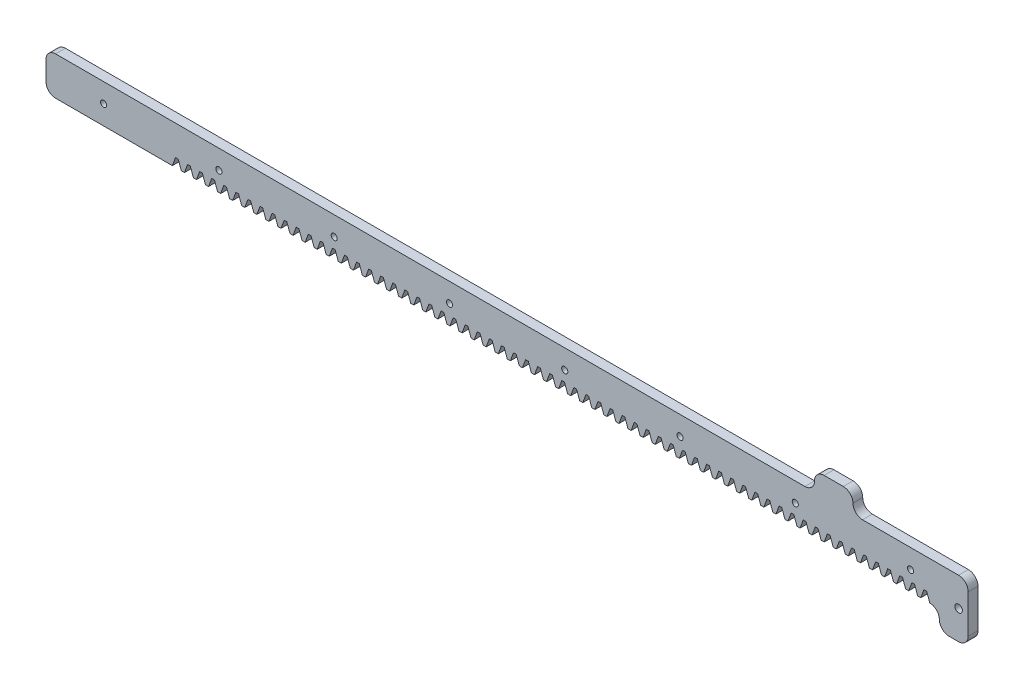
SolidWorks part; units mm, degrees
material "PC High Viscosity"
ref_plane "Front Plane" through (0, 0, 0) normal (0, 0, 1) x (1, 0, 0)
ref_plane "Top Plane" through (0, 0, 0) normal (0, 1, 0) x (1, 0, 0)
ref_plane "Right Plane" through (0, 0, 0) normal (1, 0, 0) x (0, 0, -1)
sketch "Sketch1" plane through (0, 0, 0) normal (0, 0, 1) x (1, 0, 0)
  line L0 (533.4, 25.4) -> (533.4, 38.1)
  line L1 (0, 0) -> (590.55, 0)
  line L2 (0, 0) -> (0, 25.4)
  line L3 (0, 25.4) -> (508, 25.4)
  line L4 (609.6, 0) -> (609.6, 25.4)
  line L5 (533.4, 38.1) -> (508, 38.1)
  line L6 (508, 38.1) -> (508, 25.4)
  line L7 (533.4, 25.4) -> (609.6, 25.4)
  line L10 (590.55, 0) -> (590.55, -12.7)
  line L11 (609.6, 10.0162) -> (603.25, 13.6823) construction
  line L12 (603.25, 13.6823) -> (596.9, 10.0162) construction
  line L13 (596.9, 10.0162) -> (596.9, 2.6838) construction
  line L14 (596.9, 2.6838) -> (603.25, -0.9823) construction
  line L15 (603.25, -0.9823) -> (609.6, 2.6838) construction
  line L16 (609.6, 2.6838) -> (609.6, 10.0162) construction
  line L17 (609.6, 0) -> (609.6, -12.7)
  line L18 (609.6, -12.7) -> (590.55, -12.7)
  line L19 (590.55, 0) -> (590.55, 10.0162) construction
  line L20 (590.55, 10.0162) -> (76.2, 10.0162) construction
  line L21 (76.2, 10.0162) -> (76.2, 0) construction
  circle A0 centre (603.25, 6.35) radius 2.4892
  circle A1 centre (603.25, 6.35) radius 6.35 construction
  dimension "D5" = 4.9784
  dimension "D6" = 76.2
  dimension "D7" = 12.7
  dimension "D1" = 609.6
  dimension "D2" = 25.4
  dimension "D3" = 25.4
  dimension "D4" = 12.7
  dimension "D8" = 19.05
  dimension "D9" = 12.7
extrude "Boss-Extrude1" add sketch "Sketch1" along normal blind 6.477 contours L3 | L1 L4 L3 L2 A0 | L1 region at (313.2393, 12.8036, 0)
fillet "Fillet2" radius 6.35 10 edges at (0, 0, 3.2385) (0, 25.4, 3.2385) (590.55, 0, 3.2385) (590.55, -12.7, 3.2385) (609.6, -12.7, 3.2385) (508, 25.4, 3.2385) (508, 38.1, 3.2385) (533.4, 38.1, 3.2385) (533.4, 25.4, 3.2385) (609.6, 25.4, 3.2385)
sketch "Sketch2" plane through (0, 0, 6.477) normal (0, 0, 1) x (1, 0, 0)
  line L0 (584.2, 0) -> (82.55, 0)
  line L1 (82.55, 0) -> (82.55, 5.715)
  line L2 (82.55, 5.715) -> (584.2, 5.715)
  line L3 (584.2, 5.715) -> (584.2, 0)
  line L5 (583.2755, 2.54) -> (575.111, 2.54) construction
  line L6 (584.2, 0) -> (582.1199, 5.715)
  line L7 (82.55, 0) -> (584.2, 0) construction
  line L8 (578.2688, 0) -> (584.2, 0)
  line L9 (579.389, 0) -> (584.2, 0)
  line L10 (582.1199, 5.715) -> (580.3488, 5.715)
  line L11 (584.2, 0) -> (578.2688, 0)
  line L12 (578.2688, 0) -> (580.3488, 5.715)
  line L13 (580.3488, 5.715) -> (582.1199, 5.715)
  line L14 (584.2, 0) -> (578.2688, 0)
  line L15 (580.3488, 5.715) -> (582.1199, 5.715)
  line L16 (584.2, 0) -> (578.2688, 0)
  line L17 (578.2688, 0) -> (576.0355, 0)
  line L19 (582.1199, 5.715) -> (580.3488, 5.715) construction
  line L20 (578.2688, 0) -> (576.0355, 0) construction
  point P8 (579.1932, 2.54)
  point P16 (583.2755, 2.54)
  point P17 (575.111, 2.54)
  dimension "D1" = 70
  dimension "D2" = 2.54
  dimension "D3" = 3.175
  dimension "D4" = 70
  dimension "D5" = 1.7711
extrude "Cut-Extrude1" cut sketch "Sketch2" against normal through all contours L12 L0 L8 L6 L2 region at (581.2344, 2.343, 6.477)
pattern_linear "LPattern1" count 63 spacing 7.9796 along (-1, 0, 0) of "Cut-Extrude1"
sketch "Sketch3" plane through (0, 0, 6.477) normal (0, 0, 1) x (1, 0, 0)
  line L0 (82.55, 25.4) -> (603.25, 25.4) construction
  line L1 (609.6, 19.05) -> (609.6, -6.35) construction
  circle A0 centre (571.5, 12.7) radius 2.0193
  dimension "D2" = 4.0386
  dimension "D4" = 12.7
  dimension "D5" = 38.1
extrude "Cut-Extrude2" cut sketch "Sketch3" against normal through all
pattern_linear "LPattern2" count 8 spacing 76.2 along (-1, 0, 0) of "Cut-Extrude2"
